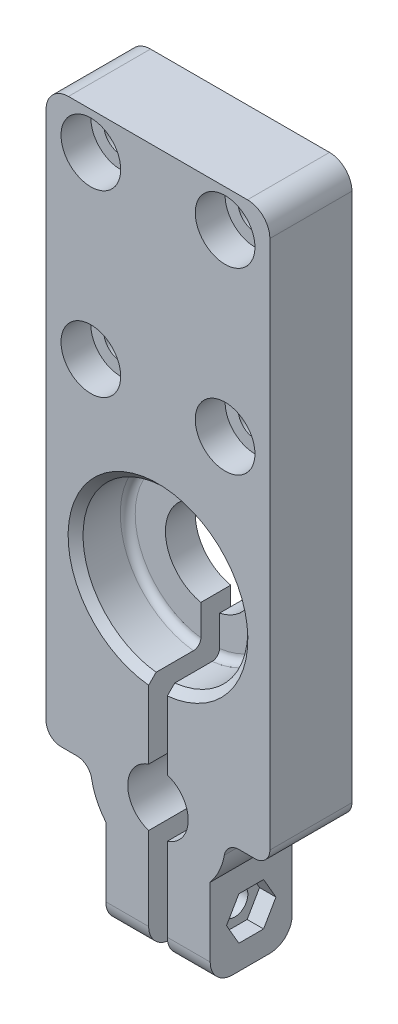
SolidWorks part; units mm, degrees
material "ABS"
ref_plane "Front Plane" through (0, 0, 0) normal (0, 0, 1) x (1, 0, 0)
ref_plane "Top Plane" through (0, 0, 0) normal (0, 1, 0) x (1, 0, 0)
ref_plane "Right Plane" through (0, 0, 0) normal (1, 0, 0) x (0, 0, -1)
sketch "Sketch2" plane through (0, 0, 0) normal (0, 0, 1) x (1, 0, 0)
  line L1 (-15, -17) -> (15, -17)
  line L2 (-15, -17) -> (-15, 17)
  line L3 (-15, 17) -> (15, 17)
  line L4 (15, -17) -> (15, 17)
  line L5 (-15, -17) -> (15, 17) construction
  line L6 (-15, 17) -> (15, -17) construction
  line L7 (-9, -12) -> (9, -12) construction
  line L8 (-9, -12) -> (-9, 12) construction
  line L9 (-9, 12) -> (9, 12) construction
  line L10 (9, -12) -> (9, 12) construction
  line L11 (-9, -12) -> (9, 12) construction
  line L12 (-9, 12) -> (9, -12) construction
  point P0 (0, 0)
  point P6 (0, 0)
  dimension "D1" = 34
  dimension "D2" = 30
  dimension "D3" = 5
  dimension "D4" = 6
extrude "Boss-Extrude1" add sketch "Sketch2" along normal blind 11 contours L3 L4 L1 L2
hole_wizard "CBORE for M4 SHCS1" positions "Sketch3" profile "Sketch4" counterbore size "M4" standard "ANSI Metric" end condition through all
sketch "Sketch3" plane through (0, 0, 11) normal (0, 0, 1) x (1, 0, 0)
  point P0 (-9, 12)
  point P3 (9, 12)
  point P6 (-9, -12)
  point P9 (9, -12)
sketch "Sketch4" plane through (-9, 12, 11) normal (1, 0, 0) x (0, -1, 0)
  line L0 (0, 0) -> (0, 11)
  line L1 (0, 11) -> (2.25, 11)
  line L3 (2.25, 11) -> (2.25, 4)
  line L4 (2.25, 4) -> (4, 4)
  line L5 (4, 4) -> (4, 0)
  line L7 (4, 0) -> (0, 0)
  line L11 (0, -6.35) -> (0, 107.95) construction
  dimension "Thru Hole Dia." = 4.5
  dimension "Thru Hole Depth" = 11
  dimension "C'Bore Dia." = 8
  dimension "C'Bore Depth" = 4
sketch "Sketch6" plane through (0, 0, 0) normal (0, 0, 1) x (1, 0, 0)
  line L0 (15, -17) -> (15, 17) construction
  line L1 (-15, -17) -> (15, -17)
  line L2 (-15, -17) -> (-15, -77)
  line L3 (-15, -77) -> (15, -77)
  line L4 (15, -17) -> (15, -77)
  circle A0 centre (0, -34) radius 11.05
  circle A1 centre (0, -59) radius 4.05
  dimension "D1" = 22.1
  dimension "D3" = 8.1
  dimension "D2" = 59
  dimension "D4" = 60
  dimension "D5" = 34
extrude "Boss-Extrude2" add sketch "Sketch6" along normal up to surface (11 mm away) up to face at (-5, 12, 11)
sketch "Sketch8" plane through (0, 0, 0) normal (0, 0, 1) x (1, 0, 0)
  circle A0 centre (0, -34) radius 6
  circle A1 centre (0, -34) radius 11.05
  circle A2 centre (0, -34) radius 11.05 construction
  dimension "D1" = 12
extrude "Boss-Extrude3" add sketch "Sketch8" along normal blind 4 from surface starting at face at (-6.75, 12, 0)
sketch "Sketch7" plane through (0, 0, 11) normal (0, 0, 1) x (1, 0, 0)
  line L0 (-1.25, -77) -> (-1.25, 0)
  line L5 (-7, -64.7361) -> (-7, -77)
  line L6 (-1.25, -77) -> (1.25, -77)
  line L7 (7, -64.7361) -> (7, -77)
  line L8 (-1.25, 0) -> (1.25, 0)
  line L9 (-15, 17) -> (-15, -77)
  line L10 (-15, -77) -> (15, -77)
  line L11 (15, -77) -> (15, 17)
  line L12 (15, 17) -> (-15, 17)
  line L13 (-15, 17) -> (-15, -77)
  line L15 (15, -77) -> (15, 17)
  line L16 (15, 17) -> (-15, 17)
  line L17 (-9.05, -59) -> (-15, -59)
  line L18 (9.05, -59) -> (15, -59)
  line L19 (1.25, -77) -> (1.25, 0)
  line L20 (-1.25, -77) -> (1.25, 0) construction
  line L21 (-7, -64.7361) -> (7, -64.7361) construction
  line L22 (-1.25, 0) -> (1.25, -77) construction
  line L26 (-15, -77) -> (15, -77)
  circle A0 centre (0, -34) radius 11.05 construction
  circle A1 centre (0, -34) radius 11.05
  circle A4 centre (0, -59) radius 9.05
  circle A5 centre (0, -59) radius 9.05
  point P0 (0, 0)
  point P1 (0, -38.5)
  line M10 (-15, -77) -> (15, -77)
  line M11 (15, -77) -> (15, 17)
  circle M13 centre (0, -59) radius 4.05
  circle M14 centre (0, -34) radius 11.05
  dimension "D3" = 14
  dimension "D4" = 2.5
  dimension "D1" = 0
  dimension "D2" = 5
extrude "Cut-Extrude1" cut sketch "Sketch7" against normal through all and the other way through all contours A5 L17 L13 L5 M10 | A5 L7 L18 M10 M11 | A5 L0 L19 M10 | L19 A5 L0 M13 | A5 L19 L0 M14 | L19 L0 M14 | L0 A5 L19 M13 region at (0, -72.5105, 11) region at (0, -65.5027, 11) region at (-11.1874, -68.4026, 11) region at (11.1874, -68.4026, 11) region at (0, -52.4973, 11) region at (0, -47.5026, 11) region at (0, -34, 11)
fillet "Fillet2" radius 2 4 edges at (15, -59, 5.5) (-15, -59, 5.5) (-9.05, -59, 5.5) (9.05, -59, 5.5)
fillet "Fillet3" radius 1 2 edges at (-11.05, -34, 4) (11.05, -34, 4)
sketch "Sketch9" plane through (7, 0, 0) normal (1, 0, 0) x (0, 0, -1)
  line L0 (-11, -64.7361) -> (-11, -77) construction
  line L1 (-11, -77) -> (-11, -64.7361) construction
  line L2 (0, -77) -> (-11, -77) construction
  line L4 (-2.186, -70.868) -> (-3.843, -67.998)
  line L5 (-3.843, -67.998) -> (-7.157, -67.998)
  line L6 (-7.157, -67.998) -> (-8.814, -70.868)
  line L7 (-8.814, -70.868) -> (-7.157, -73.738)
  line L8 (-7.157, -73.738) -> (-3.843, -73.738)
  line L9 (-3.843, -73.738) -> (-2.186, -70.868)
  circle A0 centre (-5.5, -70.868) radius 1.75
  circle A1 centre (-5.5, -70.868) radius 2.87 construction
  point P7 (-11, -70.868)
  point P11 (-5.5, -77)
  dimension "D1" = 3.5
  dimension "D2" = 5.74
extrude "Cut-Extrude2" cut sketch "Sketch9" against normal through all contours A0
extrude "Cut-Extrude3" cut sketch "Sketch9<3>" against normal blind 2.2
sketch "Sketch9<3>" plane through (7, 0, 0) normal (1, 0, 0) x (0, 0, -1) same geometry as "Sketch9"
fillet "Fillet4" radius 3 6 edges at (-15, 17, 5.5) (15, 17, 5.5) (4.125, -77, 0) (4.125, -77, 11) (-4.125, -77, 11) (-4.125, -77, 0)
chamfer "Chamfer1" distance 1 angle 45 1 edges at (0, -22.95, 11)
